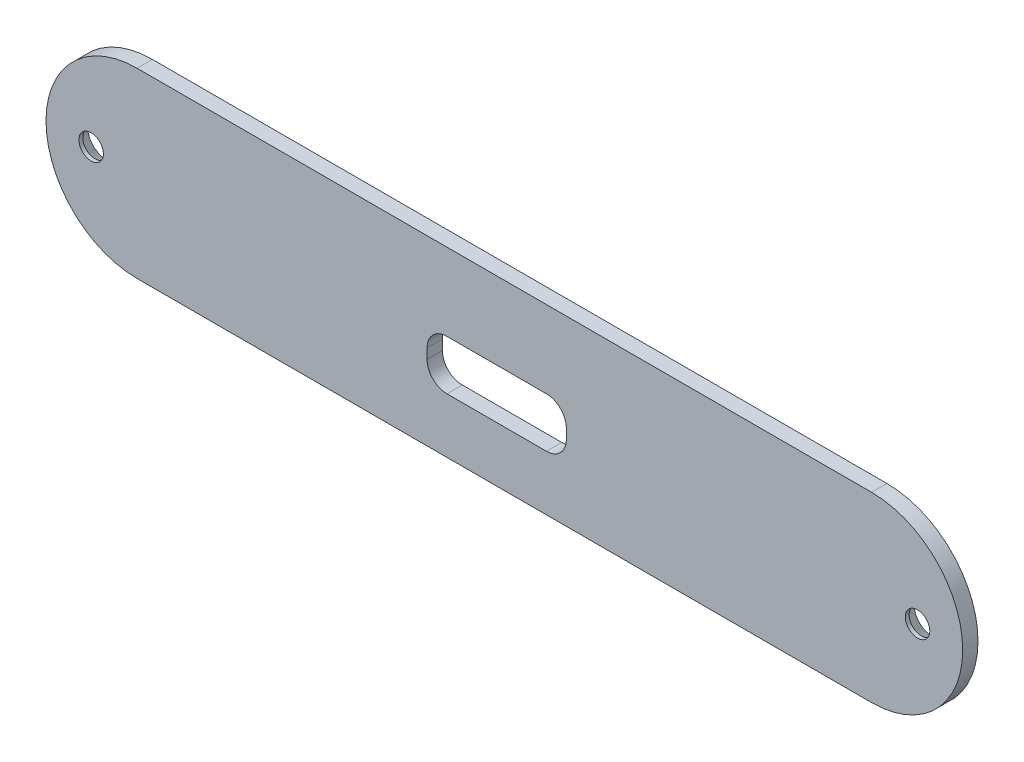
SolidWorks part; units mm, degrees
ref_plane "Front Plane" through (0, 0, 0) normal (0, 0, 1) x (1, 0, 0)
ref_plane "Top Plane" through (0, 0, 0) normal (0, 1, 0) x (1, 0, 0)
ref_plane "Right Plane" through (0, 0, 0) normal (1, 0, 0) x (0, 0, -1)
sketch "Sketch1" plane through (0, 0, 0) normal (0, 0, 1) x (1, 0, 0)
  line L0 (0, 0) -> (0, 16.0369) construction
  line L1 (30.5, 0) -> (-30.5, 0) construction
  line L2 (24, 6.5) -> (-24, 6.5)
  line L3 (24, -6.5) -> (-24, -6.5)
  line L4 (0, 0) -> (0, -11.8688) construction
  line L5 (24, 5.5) -> (-24, 5.5)
  line L6 (-24, -5.5) -> (24, -5.5)
  line L7 (27, 1.7) -> (27.7947, 1.7)
  line L8 (26, 0.5) -> (26, 0.7)
  line L9 (-26, -0.5) -> (-26.441, -0.5)
  line L10 (-26.441, 0.5) -> (-26, 0.5)
  line L11 (-26, -5.1235) -> (-26, -3.375)
  line L12 (-26, -3.375) -> (-26.5557, -3.375)
  line L13 (-26.5557, -2.325) -> (-26, -2.325)
  line L14 (-26, -2.325) -> (-26, -0.5)
  line L15 (-26, 0.5) -> (-26, 0.7)
  line L16 (-27, 1.7) -> (-27.7947, 1.7)
  line L17 (26, -2.325) -> (26, -0.5)
  line L18 (26.5557, -2.325) -> (26, -2.325)
  line L19 (26, -3.375) -> (26.5557, -3.375)
  line L20 (26, -5.1235) -> (26, -3.375)
  line L21 (26.441, 0.5) -> (26, 0.5)
  line L22 (26, -0.5) -> (26.441, -0.5)
  arc A0 (-24, 6.5) -> (-24, -6.5) centre (-24, 0) ccw
  arc A1 (-24, 5.5) -> (-28.5372, 3.1087) centre (-24, 0) ccw
  arc A2 (-26.5557, -2.325) -> (-26.5557, -3.375) centre (-27.465, -2.85) ccw
  arc A3 (-26.441, 0.5) -> (-26.441, -0.5) centre (-27, 0) ccw
  arc A4 (-27, 1.7) -> (-26, 0.7) centre (-27, 0.7) cw
  arc A5 (-26, -5.1235) -> (-24, -5.5) centre (-24, 0) ccw
  arc A6 (-27.7947, 1.7) -> (-28.5372, 3.1087) centre (-27.7947, 2.6) cw
  arc A7 (27.7947, 1.7) -> (28.5372, 3.1087) centre (27.7947, 2.6) ccw
  arc A8 (26, -5.1235) -> (24, -5.5) centre (24, 0) cw
  arc A9 (27, 1.7) -> (26, 0.7) centre (27, 0.7) ccw
  arc A10 (26.441, 0.5) -> (26.441, -0.5) centre (27, 0) cw
  arc A11 (26.5557, -2.325) -> (26.5557, -3.375) centre (27.465, -2.85) cw
  arc A12 (24, 5.5) -> (28.5372, 3.1087) centre (24, 0) cw
  arc A13 (24, 6.5) -> (24, -6.5) centre (24, 0) cw
  point P6 (0, 6.5)
  point P10 (0, -6.5)
  point P15 (0, 5.5)
  point P23 (-30.5, 0)
  point P56 (0, -5.5)
  dimension "D2" = 6.5
  dimension "D4" = 5.5
  dimension "D5" = 2.1
  dimension "D6" = 1.5
  dimension "D7" = 27
  dimension "D8" = 30.5
  dimension "D16" = 1
  dimension "D17" = 0.9
  dimension "D19" = 1.7
  dimension "D1" = 13
  dimension "D3" = 1
  dimension "D9" = 27.465
  dimension "D10" = 1
  dimension "D11" = 0.5
  dimension "D12" = 26
  dimension "D13" = 1.05
  dimension "D14" = 0.525
  dimension "D15" = 3.65
  dimension "D20" = 1
extrude "Boss-Extrude1" [suppressed] add sketch "Sketch1" along normal blind 25 and the other way blind 25
sketch "Sketch2" [suppressed] plane through (0, 0, 25) normal (0, 0, 1) x (1, 0, 0)
  line L0 (24, 6.5) -> (-24, 6.5) construction
  line L1 (-24, -6.5) -> (24, -6.5) construction
  line L2 (24, 6.5) -> (-24, 6.5) construction
  line L3 (-24, -6.5) -> (24, -6.5) construction
  line L4 (24, 6) -> (-24, 6)
  line L5 (-24, -6) -> (24, -6)
  arc A0 (-24, 6.5) -> (-24, -6.5) centre (-24, 0) ccw construction
  arc A1 (24, -6.5) -> (24, 6.5) centre (24, 0) ccw construction
  arc A2 (-24, 6.5) -> (-24, -6.5) centre (-24, 0) ccw construction
  arc A3 (24, -6.5) -> (24, 6.5) centre (24, 0) ccw construction
  arc A4 (-24, 6) -> (-24, -6) centre (-24, 0) ccw
  arc A5 (24, -6) -> (24, 6) centre (24, 0) ccw
  dimension "D1" = 0.5
sketch "Sketch3" plane through (0, 0, 0) normal (0, 0, 1) x (1, 0, 0)
  line L2 (24, 5.95) -> (-24, 5.95)
  line L3 (-24, -5.95) -> (24, -5.95)
  line L4 (-24, 0) -> (24, 0) construction
  line L5 (0, 5.95) -> (0, -5.95) construction
  arc A2 (-24, 5.95) -> (-24, -5.95) centre (-24, 0) ccw
  arc A3 (24, -5.95) -> (24, 5.95) centre (24, 0) ccw
  point P12 (0, 0)
  point P13 (0, -5.95)
  point P15 (0, 5.95)
  point P18 (0, 0)
  dimension "D2" = 5.95
  dimension "D3" = 11.9
  dimension "D1" = 48
extrude "Boss-Extrude2" add sketch "Sketch3" along normal blind 1
sketch "Sketch4" plane through (0, 0, 1) normal (0, 0, 1) x (1, 0, 0)
  line L0 (-27, 0) -> (27, 0) construction
  circle A0 centre (-27, 0) radius 0.8
  circle A1 centre (27, 0) radius 0.8
  point P4 (0, 0)
  dimension "D1" = 1.6
  dimension "D2" = 27
extrude "Cut-Extrude1" cut sketch "Sketch4" against normal through all contours A0 | A1
sketch "Sketch5" plane through (0, 0, 0) normal (0, 0, -1) x (-1, 0, 0)
  line L0 (-24, 5.95) -> (24, 5.95) construction
  line L1 (-4.05, -2.35) -> (5.05, -2.35)
  line L2 (-4.05, -2.35) -> (-4.05, 0.9)
  line L3 (-4.05, 0.9) -> (5.05, 0.9)
  line L4 (5.05, -2.35) -> (5.05, 0.9)
  dimension "D1" = 9.1
  dimension "D2" = 3.25
  dimension "D3" = 5.05
  dimension "D4" = 5.05
extrude "Cut-Extrude2" cut sketch "Sketch5" against normal through all
fillet "Fillet1" radius 1.3 4 edges at (4.05, 0.9, 0.5) (-5.05, 0.9, 0.5) (4.05, -2.35, 0.5) (-5.05, -2.35, 0.5)
chamfer "Chamfer1" distance 0.75 angle 30 2 edges at (27.8, 0, 0) (-26.2, 0, 0) first distance on face at (27.8, 0, 0) first distance on face at (-26.2, 0, 0)
